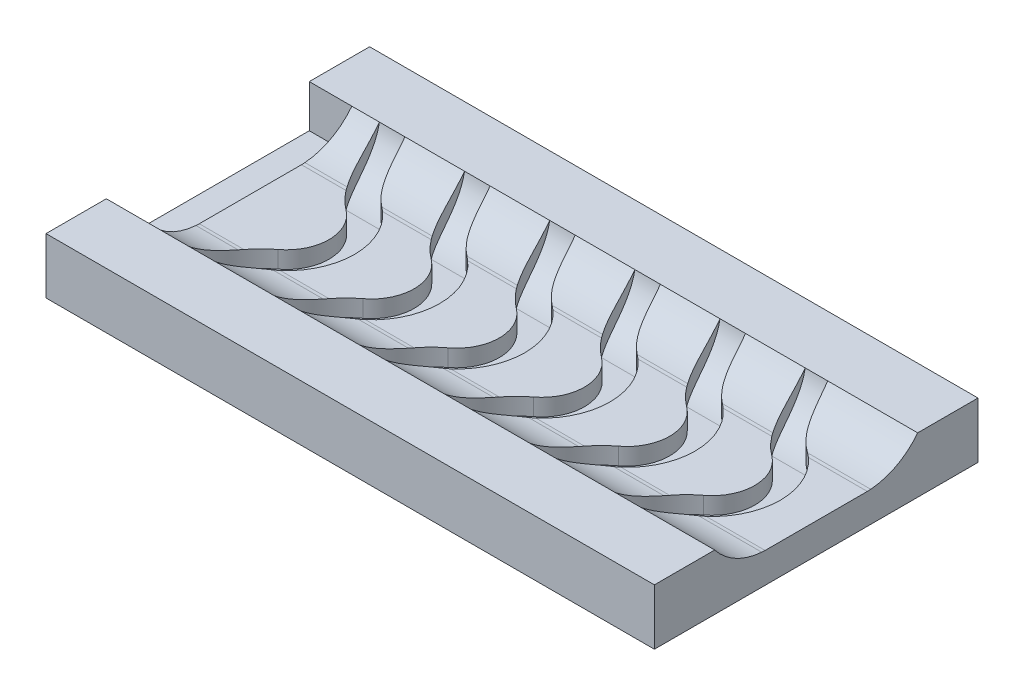
SolidWorks part; units mm, degrees
ref_plane "Front Plane" through (0, 0, 0) normal (0, 0, 1) x (1, 0, 0)
ref_plane "Top Plane" through (0, 0, 0) normal (0, 1, 0) x (1, 0, 0)
ref_plane "Right Plane" through (0, 0, 0) normal (1, 0, 0) x (0, 0, -1)
sketch "Sketch1" plane through (0, 0, 0) normal (0, 1, 0) x (1, 0, 0)
  line L0 (-64.0369, -7.1498) -> (-64.0369, -31.1498)
  line L1 (-64.0369, -31.1498) -> (-8.0369, -31.1498)
  line L2 (-8.0369, -31.1498) -> (-8.0369, -7.1498)
  line L3 (-8.0369, -7.1498) -> (-64.0369, -7.1498)
  line L4 (-8.0369, -31.1498) -> (-8.0369, -38.1498)
  line L5 (-8.0369, -38.1498) -> (-71.0369, -38.1498)
  line L6 (-71.0369, -38.1498) -> (-71.0369, -0.1498)
  line L7 (-71.0369, -0.1498) -> (-1.0369, -0.1498)
  line L8 (-1.0369, -0.1498) -> (-1.0369, -38.1498)
  line L9 (-1.0369, -38.1498) -> (-8.0369, -38.1498)
extrude "Boss-Extrude1" add sketch "Sketch1" along normal blind 10 contours L9 L8 L7 L6 L5 L1 L0 L3 L2 region at (-39.5369, 0, 37.3533)
sketch "Sketch2" plane through (0, 0, 0) normal (0, -1, 0) x (1, 0, 0)
  line L4 (-71.0369, 38.1498) -> (-71.0369, 0.1498)
  line L5 (-71.0369, 0.1498) -> (-1.0369, 0.1498)
  line L6 (-1.0369, 0.1498) -> (-1.0369, 38.1498)
  line L7 (-1.0369, 38.1498) -> (-71.0369, 38.1498)
  line L8 (-71.0369, 38.1498) -> (-71.0369, 0.1498)
  line L9 (-71.0369, 0.1498) -> (-1.0369, 0.1498)
  line L10 (-1.0369, 0.1498) -> (-1.0369, 38.1498)
  line L11 (-1.0369, 38.1498) -> (-71.0369, 38.1498)
  dimension "D1" = 0
extrude "Boss-Extrude2" add sketch "Sketch2" against normal blind 7
sketch "Sketch3" plane through (0, 7, 0) normal (0, 1, 0) x (1, 0, 0)
  line L0 (-64.0369, -19.1498) -> (-8.0369, -19.1498)
  line L1 (-64.0369, -7.1498) -> (-64.0369, -31.1498) construction
  line L2 (-8.0369, -7.1498) -> (-8.0369, -31.1498) construction
  line L3 (-64.0369, -19.1498) -> (-64.0369, -31.1498)
  line L4 (-64.0369, -19.1498) -> (-64.0369, -7.1498)
  line L8 (-50.2791, -19.1498) -> (-51.4339, -19.1498)
  circle A14 centre (-18.2485, -19.1498) radius 5
  circle A15 centre (-18.2485, -19.1498) radius 8
  circle A16 centre (-18.2485, -19.1498) radius 15
  circle A17 centre (-9.2485, -7.1498) radius 10
  circle A18 centre (-9.6097, -6.8872) radius 7
  circle A19 centre (-9.2485, -31.1498) radius 7
  circle A20 centre (-9.2485, -31.1498) radius 10
  line M7 (-8.0369, -7.1498) -> (-64.0369, -7.1498)
  line M9 (-64.0369, -31.1498) -> (-8.0369, -31.1498)
extrude "Cut-Extrude8" cut sketch "Sketch3" against normal blind 2 contours A20 A15 L0 A14 | A17 A14 L0 A15 | A15 A17 | A18 A17 A15 M7 | A15 A20 | A15 A20 A19 M9 region at (-17.2418, 7, 28.9232) region at (-17.3783, 7, 9.3878) region at (-14.3694, 7, 24.3219) region at (-14.3694, 7, 13.9776) region at (-12.1287, 7, 20.5083) region at (-12.1287, 7, 17.7912)
sketch "Sketch4" plane through (0, 7, 0) normal (0, 1, 0) x (1, 0, 0)
  line L0 (-13.2485, -19.1498) -> (-28.2485, -19.1498)
  line L1 (-16.6047, -7.1498) -> (-8.0369, -7.1498) construction
  line L2 (-64.0369, -31.1498) -> (-8.0369, -31.1498) construction
  arc A0 (-15.2485, -23.1498) -> (-15.2485, -15.1498) centre (-18.2485, -19.1498) ccw construction
  circle A1 centre (-28.2485, -19.1498) radius 5
  circle A2 centre (-28.2485, -19.1498) radius 8
  circle A3 centre (-28.2485, -19.1498) radius 15
  circle A4 centre (-19.2485, -7.1498) radius 10
  circle A5 centre (-19.2485, -7.1498) radius 7
  circle A6 centre (-19.2485, -31.1498) radius 10
  circle A7 centre (-19.2485, -31.1498) radius 7
  line M5 (-19.2485, -7.1498) -> (-64.0369, -7.1498)
  line M7 (-64.0369, -31.1498) -> (-19.2485, -31.1498)
extrude "Cut-Extrude10" cut sketch "Sketch4" against normal blind 2 contours A5 A4 A2 M5 | A2 A4 | A4 A1 L0 A2 | A6 A2 L0 A1 | A2 A6 | A7 A2 A6 M7 region at (-22.1287, 7, 20.5083) region at (-22.1287, 7, 17.7912) region at (-24.3694, 7, 13.9776) region at (-24.3694, 7, 24.3219) region at (-27.2418, 7, 9.3764) region at (-27.2418, 7, 28.9232)
sketch "Sketch5" plane through (0, 7, 0) normal (0, 1, 0) x (1, 0, 0)
  line L0 (-23.2485, -19.1498) -> (-38.2485, -19.1498)
  arc A0 (-25.2485, -23.1498) -> (-25.2485, -15.1498) centre (-28.2485, -19.1498) ccw construction
  circle A1 centre (-38.2485, -19.1498) radius 5
  circle A2 centre (-38.2485, -19.1498) radius 8
  circle A3 centre (-38.2485, -19.1498) radius 15
  circle A4 centre (-29.2485, -31.1498) radius 10
  circle A5 centre (-29.2485, -31.1498) radius 7
  circle A6 centre (-29.2485, -7.1498) radius 10
  circle A7 centre (-29.2485, -7.1498) radius 7
  line M4 (-64.0369, -31.1498) -> (-29.2485, -31.1498)
  line M8 (-29.2485, -7.1498) -> (-64.0369, -7.1498)
extrude "Cut-Extrude11" cut sketch "Sketch5" against normal blind 2 contours A7 A6 A2 M8 | A2 A6 | A6 A1 L0 A2 | A4 A2 L0 A1 | A2 A4 | A5 A2 A4 M4 region at (-32.1287, 7, 20.5083) region at (-32.1287, 7, 17.7912) region at (-34.3694, 7, 13.9776) region at (-34.3694, 7, 24.3219) region at (-37.2418, 7, 9.3764) region at (-37.2418, 7, 28.9232)
sketch "Sketch6" plane through (0, 7, 0) normal (0, 1, 0) x (1, 0, 0)
  line L0 (-33.2485, -19.1498) -> (-48.2485, -19.1498)
  arc A0 (-35.2485, -23.1498) -> (-35.2485, -15.1498) centre (-38.2485, -19.1498) ccw construction
  circle A1 centre (-48.2485, -19.1498) radius 5
  circle A2 centre (-48.2485, -19.1498) radius 8
  circle A3 centre (-48.2485, -19.1498) radius 15
  circle A4 centre (-39.2485, -31.1498) radius 10
  circle A5 centre (-39.2485, -31.1498) radius 7
  circle A6 centre (-39.2485, -7.1498) radius 10
  arc A7 (-39.2485, -7.1498) -> (-35.2485, -15.1498) centre (-29.2485, -7.1498) ccw construction
  circle A8 centre (-39.2485, -7.1498) radius 7
  line M1 (-64.0369, -31.1498) -> (-39.2485, -31.1498)
  line M5 (-39.2485, -7.1498) -> (-64.0369, -7.1498)
extrude "Cut-Extrude12" cut sketch "Sketch6" against normal blind 2 contours A8 A6 A2 M5 | A2 A6 | A6 A1 L0 A2 | A4 A2 L0 A1 | A2 A4 | A5 A2 A4 M1 region at (-42.1287, 7, 20.5083) region at (-42.1287, 7, 17.7912) region at (-44.3694, 7, 13.9776) region at (-44.3694, 7, 24.3219) region at (-47.2418, 7, 9.3764) region at (-47.2418, 7, 28.9232)
sketch "Sketch7" plane through (0, 7, 0) normal (0, 1, 0) x (1, 0, 0)
  line L0 (-43.2485, -19.1498) -> (-58.2485, -19.1498)
  arc A0 (-45.2485, -23.1498) -> (-45.2485, -15.1498) centre (-48.2485, -19.1498) ccw construction
  circle A1 centre (-58.2485, -19.1498) radius 5
  circle A2 centre (-58.2485, -19.1498) radius 8
  circle A3 centre (-58.2485, -19.1498) radius 15
  circle A4 centre (-49.2485, -31.1498) radius 10
  circle A5 centre (-49.2485, -31.1498) radius 7
  circle A6 centre (-49.2485, -7.1498) radius 10
  circle A7 centre (-49.2485, -7.1498) radius 7
  line M1 (-64.0369, -31.1498) -> (-49.2485, -31.1498)
  line M5 (-49.2485, -7.1498) -> (-64.0369, -7.1498)
extrude "Cut-Extrude13" cut sketch "Sketch7" against normal blind 2 contours A7 A6 A2 M5 | A2 A6 | A6 A1 L0 A2 | A4 A2 L0 A1 | A2 A4 | A5 A2 A4 M1 region at (-52.1287, 7, 20.5083) region at (-52.1287, 7, 17.7912) region at (-54.3694, 7, 13.9776) region at (-54.3694, 7, 24.3219) region at (-57.2418, 7, 9.3764) region at (-57.2418, 7, 28.9232)
sketch "Sketch8" plane through (0, 7, 0) normal (0, 1, 0) x (1, 0, 0)
  line L0 (-53.2485, -19.1498) -> (-68.2485, -19.1498)
  arc A0 (-55.2485, -23.1498) -> (-55.2485, -15.1498) centre (-58.2485, -19.1498) ccw construction
  circle A1 centre (-68.2485, -19.1498) radius 5
  circle A2 centre (-68.2485, -19.1498) radius 8
  line M6 (-64.0369, -7.1498) -> (-64.0369, -31.1498)
extrude "Cut-Extrude14" cut sketch "Sketch8" against normal blind 2 contours L0 A2 A1 M6 | A2 L0 A1 M6 region at (-62.3799, 7, 21.9464) region at (-62.3799, 7, 16.3531)
sketch "Sketch9" plane through (0, 10, 0) normal (0, 1, 0) x (1, 0, 0)
  line L0 (-8.0369, -7.1498) -> (-5.1643, -7.1498)
  line L1 (-5.1643, -7.1498) -> (-5.1643, -31.1498)
  line L2 (-5.1643, -31.1498) -> (-8.0369, -31.1498)
  line L3 (-8.0369, -31.1498) -> (-8.0369, -7.1498)
extrude "Cut-Extrude15" cut sketch "Sketch9" against normal blind 5
sketch "Sketch10" plane through (-5.1643, 0, 0) normal (-1, 0, 0) x (0, 0, 1)
  line L4 (31.1498, 10) -> (7.1498, 10)
  line L5 (7.1498, 10) -> (7.1498, 5)
  line L6 (7.1498, 5) -> (31.1498, 5)
  line L7 (31.1498, 5) -> (31.1498, 10)
  line L8 (31.1498, 10) -> (7.1498, 10)
  line L9 (7.1498, 10) -> (7.1498, 5)
  line L10 (7.1498, 5) -> (31.1498, 5)
  line L11 (31.1498, 5) -> (31.1498, 10)
  dimension "D1" = 0
extrude "Cut-Extrude16" cut sketch "Sketch10" against normal blind 18
sketch "Sketch12" plane through (0, 7, 0) normal (0, 1, 0) x (1, 0, 0)
  line L0 (-16.2485, -31.1498) -> (-8.0369, -31.1498) construction
  line L1 (-8.0369, -31.1498) -> (-8.0369, -7.1498) construction
  line L2 (-8.0369, -7.1498) -> (-16.6047, -7.1498) construction
  line L3 (-26.2485, -31.1498) -> (-19.2485, -31.1498) construction
  line L4 (-19.2485, -7.1498) -> (-26.2485, -7.1498) construction
  line L5 (-36.2485, -31.1498) -> (-29.2485, -31.1498) construction
  line L6 (-29.2485, -7.1498) -> (-36.2485, -7.1498) construction
  line L7 (-46.2485, -31.1498) -> (-39.2485, -31.1498) construction
  line L8 (-39.2485, -7.1498) -> (-46.2485, -7.1498) construction
  line L9 (-56.2485, -31.1498) -> (-49.2485, -31.1498) construction
  line L10 (-49.2485, -7.1498) -> (-56.2485, -7.1498) construction
  line L11 (-64.0369, -7.1498) -> (-64.0369, -12.3481) construction
  line L12 (-64.0369, -25.9514) -> (-64.0369, -31.1498) construction
  line L13 (-64.0369, -31.1498) -> (-59.2485, -31.1498) construction
  line L14 (-59.2485, -7.1498) -> (-64.0369, -7.1498) construction
  line L15 (-64.0369, -16.4548) -> (-64.0369, -21.8447) construction
  line L16 (-16.2485, -31.1498) -> (-8.0369, -31.1498)
  line L17 (-8.0369, -31.1498) -> (-8.0369, -7.1498)
  line L18 (-8.0369, -7.1498) -> (-16.6047, -7.1498)
  line L19 (-26.2485, -31.1498) -> (-19.2485, -31.1498)
  line L20 (-19.2485, -7.1498) -> (-26.2485, -7.1498)
  line L21 (-36.2485, -31.1498) -> (-29.2485, -31.1498)
  line L22 (-29.2485, -7.1498) -> (-36.2485, -7.1498)
  line L23 (-46.2485, -31.1498) -> (-39.2485, -31.1498)
  line L24 (-39.2485, -7.1498) -> (-46.2485, -7.1498)
  line L25 (-56.2485, -31.1498) -> (-49.2485, -31.1498)
  line L26 (-49.2485, -7.1498) -> (-56.2485, -7.1498)
  line L27 (-64.0369, -7.1498) -> (-64.0369, -12.3481)
  line L28 (-64.0369, -25.9514) -> (-64.0369, -31.1498)
  line L29 (-64.0369, -31.1498) -> (-59.2485, -31.1498)
  line L30 (-59.2485, -7.1498) -> (-64.0369, -7.1498)
  line L31 (-64.0369, -16.4548) -> (-64.0369, -21.8447)
  arc A0 (-13.4485, -25.5498) -> (-13.6411, -12.6097) centre (-18.2485, -19.1498) ccw construction
  arc A1 (-13.4485, -25.5498) -> (-16.2485, -31.1498) centre (-9.2485, -31.1498) ccw construction
  arc A2 (-16.6047, -7.1498) -> (-13.6411, -12.6097) centre (-9.6097, -6.8872) ccw construction
  arc A3 (-26.2485, -7.1498) -> (-23.4485, -12.7498) centre (-19.2485, -7.1498) ccw construction
  arc A4 (-23.4485, -25.5498) -> (-23.4485, -12.7498) centre (-28.2485, -19.1498) ccw construction
  arc A5 (-23.4485, -25.5498) -> (-26.2485, -31.1498) centre (-19.2485, -31.1498) ccw construction
  arc A6 (-15.2485, -23.1498) -> (-19.2485, -31.1498) centre (-9.2485, -31.1498) ccw construction
  arc A7 (-15.2485, -23.1498) -> (-15.2485, -15.1498) centre (-18.2485, -19.1498) ccw construction
  arc A8 (-19.2485, -7.1498) -> (-15.2485, -15.1498) centre (-9.2485, -7.1498) ccw construction
  arc A9 (-36.2485, -7.1498) -> (-33.4485, -12.7498) centre (-29.2485, -7.1498) ccw construction
  arc A10 (-33.4485, -25.5498) -> (-33.4485, -12.7498) centre (-38.2485, -19.1498) ccw construction
  arc A11 (-33.4485, -25.5498) -> (-36.2485, -31.1498) centre (-29.2485, -31.1498) ccw construction
  arc A12 (-25.2485, -23.1498) -> (-29.2485, -31.1498) centre (-19.2485, -31.1498) ccw construction
  arc A13 (-25.2485, -23.1498) -> (-25.2485, -15.1498) centre (-28.2485, -19.1498) ccw construction
  arc A14 (-29.2485, -7.1498) -> (-25.2485, -15.1498) centre (-19.2485, -7.1498) ccw construction
  arc A15 (-46.2485, -7.1498) -> (-43.4485, -12.7498) centre (-39.2485, -7.1498) ccw construction
  arc A16 (-43.4485, -25.5498) -> (-43.4485, -12.7498) centre (-48.2485, -19.1498) ccw construction
  arc A17 (-43.4485, -25.5498) -> (-46.2485, -31.1498) centre (-39.2485, -31.1498) ccw construction
  arc A18 (-35.2485, -23.1498) -> (-39.2485, -31.1498) centre (-29.2485, -31.1498) ccw construction
  arc A19 (-35.2485, -23.1498) -> (-35.2485, -15.1498) centre (-38.2485, -19.1498) ccw construction
  arc A20 (-39.2485, -7.1498) -> (-35.2485, -15.1498) centre (-29.2485, -7.1498) ccw construction
  arc A21 (-56.2485, -7.1498) -> (-53.4485, -12.7498) centre (-49.2485, -7.1498) ccw construction
  arc A22 (-53.4485, -25.5498) -> (-53.4485, -12.7498) centre (-58.2485, -19.1498) ccw construction
  arc A23 (-53.4485, -25.5498) -> (-56.2485, -31.1498) centre (-49.2485, -31.1498) ccw construction
  arc A24 (-45.2485, -23.1498) -> (-49.2485, -31.1498) centre (-39.2485, -31.1498) ccw construction
  arc A25 (-45.2485, -23.1498) -> (-45.2485, -15.1498) centre (-48.2485, -19.1498) ccw construction
  arc A26 (-49.2485, -7.1498) -> (-45.2485, -15.1498) centre (-39.2485, -7.1498) ccw construction
  arc A27 (-64.0369, -25.9514) -> (-64.0369, -12.3481) centre (-68.2485, -19.1498) ccw construction
  arc A28 (-55.2485, -23.1498) -> (-59.2485, -31.1498) centre (-49.2485, -31.1498) ccw construction
  arc A29 (-55.2485, -23.1498) -> (-55.2485, -15.1498) centre (-58.2485, -19.1498) ccw construction
  arc A30 (-59.2485, -7.1498) -> (-55.2485, -15.1498) centre (-49.2485, -7.1498) ccw construction
  arc A31 (-64.0369, -21.8447) -> (-64.0369, -16.4548) centre (-68.2485, -19.1498) ccw construction
  arc A32 (-13.4485, -25.5498) -> (-13.6411, -12.6097) centre (-18.2485, -19.1498) ccw
  arc A33 (-13.4485, -25.5498) -> (-16.2485, -31.1498) centre (-9.2485, -31.1498) ccw
  arc A34 (-16.6047, -7.1498) -> (-13.6411, -12.6097) centre (-9.6097, -6.8872) ccw
  arc A35 (-26.2485, -7.1498) -> (-23.4485, -12.7498) centre (-19.2485, -7.1498) ccw
  arc A36 (-23.4485, -25.5498) -> (-23.4485, -12.7498) centre (-28.2485, -19.1498) ccw
  arc A37 (-23.4485, -25.5498) -> (-26.2485, -31.1498) centre (-19.2485, -31.1498) ccw
  arc A38 (-15.2485, -23.1498) -> (-19.2485, -31.1498) centre (-9.2485, -31.1498) ccw
  arc A39 (-15.2485, -23.1498) -> (-15.2485, -15.1498) centre (-18.2485, -19.1498) ccw
  arc A40 (-19.2485, -7.1498) -> (-15.2485, -15.1498) centre (-9.2485, -7.1498) ccw
  arc A41 (-36.2485, -7.1498) -> (-33.4485, -12.7498) centre (-29.2485, -7.1498) ccw
  arc A42 (-33.4485, -25.5498) -> (-33.4485, -12.7498) centre (-38.2485, -19.1498) ccw
  arc A43 (-33.4485, -25.5498) -> (-36.2485, -31.1498) centre (-29.2485, -31.1498) ccw
  arc A44 (-25.2485, -23.1498) -> (-29.2485, -31.1498) centre (-19.2485, -31.1498) ccw
  arc A45 (-25.2485, -23.1498) -> (-25.2485, -15.1498) centre (-28.2485, -19.1498) ccw
  arc A46 (-29.2485, -7.1498) -> (-25.2485, -15.1498) centre (-19.2485, -7.1498) ccw
  arc A47 (-46.2485, -7.1498) -> (-43.4485, -12.7498) centre (-39.2485, -7.1498) ccw
  arc A48 (-43.4485, -25.5498) -> (-43.4485, -12.7498) centre (-48.2485, -19.1498) ccw
  arc A49 (-43.4485, -25.5498) -> (-46.2485, -31.1498) centre (-39.2485, -31.1498) ccw
  arc A50 (-35.2485, -23.1498) -> (-39.2485, -31.1498) centre (-29.2485, -31.1498) ccw
  arc A51 (-35.2485, -23.1498) -> (-35.2485, -15.1498) centre (-38.2485, -19.1498) ccw
  arc A52 (-39.2485, -7.1498) -> (-35.2485, -15.1498) centre (-29.2485, -7.1498) ccw
  arc A53 (-56.2485, -7.1498) -> (-53.4485, -12.7498) centre (-49.2485, -7.1498) ccw
  arc A54 (-53.4485, -25.5498) -> (-53.4485, -12.7498) centre (-58.2485, -19.1498) ccw
  arc A55 (-53.4485, -25.5498) -> (-56.2485, -31.1498) centre (-49.2485, -31.1498) ccw
  arc A56 (-45.2485, -23.1498) -> (-49.2485, -31.1498) centre (-39.2485, -31.1498) ccw
  arc A57 (-45.2485, -23.1498) -> (-45.2485, -15.1498) centre (-48.2485, -19.1498) ccw
  arc A58 (-49.2485, -7.1498) -> (-45.2485, -15.1498) centre (-39.2485, -7.1498) ccw
  arc A59 (-64.0369, -25.9514) -> (-64.0369, -12.3481) centre (-68.2485, -19.1498) ccw
  arc A60 (-55.2485, -23.1498) -> (-59.2485, -31.1498) centre (-49.2485, -31.1498) ccw
  arc A61 (-55.2485, -23.1498) -> (-55.2485, -15.1498) centre (-58.2485, -19.1498) ccw
  arc A62 (-59.2485, -7.1498) -> (-55.2485, -15.1498) centre (-49.2485, -7.1498) ccw
  arc A63 (-64.0369, -21.8447) -> (-64.0369, -16.4548) centre (-68.2485, -19.1498) ccw
extrude "Boss-Extrude3" add sketch "Sketch12" along normal blind 3
sketch "Sketch13" plane through (-1.0369, 0, 0) normal (1, 0, 0) x (0, 0, -1)
  line L0 (-31.1498, 5) -> (-31.1498, 11)
  line L1 (-31.1498, 11) -> (-25.1498, 11)
  line L2 (-7.1498, 5) -> (-7.1498, 11)
  line L3 (-7.1498, 11) -> (-13.1498, 11)
  circle A0 centre (-25.1498, 11) radius 6
  circle A1 centre (-13.1498, 11) radius 6
  line M1 (-31.1498, 5) -> (-31.1498, 10)
  line M7 (-7.1498, 10) -> (-7.1498, 5)
  line M8 (-7.1498, 5) -> (-31.1498, 5)
extrude "Boss-Extrude4" add sketch "Sketch13" against normal blind 149 contours A0 L0 M1 M8 | A1 L2 M8 M7 region at (-1.0369, 6.3402, 29.8095) region at (-1.0369, 6.3402, 8.49)
sketch "Sketch14" plane through (-1.0369, 0, 0) normal (1, 0, 0) x (0, 0, -1)
  line L0 (-25.1498, 7) -> (-13.1498, 7)
  line L1 (-13.1498, 7) -> (-13.1498, 15)
  line L2 (-13.1498, 15) -> (-25.1498, 15)
  circle A0 centre (-25.1498, 11) radius 4
  circle A1 centre (-13.1498, 11) radius 4
extrude "Cut-Extrude17" cut sketch "Sketch14" against normal up to surface (63 mm away) contours A0 | L1 A1 | L1 A1 | A1 L2 A0 L0 region at (-1.0369, 11, 19.1498) region at (-1.0369, 11, 25.1498) region at (-1.0369, 11, 14.8474) region at (-1.0369, 11, 11.4521) up to face at (-64.0369, 7.0081, 24.1486)
sketch "Sketch15" plane through (-1.0369, 0, 0) normal (1, 0, 0) x (0, 0, -1)
  line L0 (-38.1498, 10) -> (-0.1498, 10)
  line L1 (-0.1498, 10) -> (-0.1498, 15.8218)
  line L2 (-0.1498, 15.8218) -> (-38.1498, 15.8218)
  line L3 (-38.1498, 15.8218) -> (-38.1498, 10)
extrude "Cut-Extrude18" cut sketch "Sketch15" against normal blind 103
sketch "Sketch16" plane through (-1.0369, 0, 0) normal (1, 0, 0) x (0, 0, -1)
  line L1 (-38.1498, 0) -> (-0.1498, 0)
  line L2 (-38.1498, 0) -> (-38.1498, 10)
  line L3 (-38.1498, 10) -> (-0.1498, 10)
  line L4 (-0.1498, 0) -> (-0.1498, 10)
extrude "Boss-Extrude5" add sketch "Sketch16" against normal up to surface (7 mm away) up to face at (-8.0369, 7.5638, 19.1498)
sketch "Sketch17" plane through (-64.0369, 0, 0) normal (1, 0, 0) x (0, 0, -1)
  line L0 (-21.8447, 5) -> (-16.4548, 5)
  line L8 (-12.3481, 5.0538) -> (-12.3481, 7.0812)
  line L9 (-9.2768, 10) -> (-29.0227, 10)
  line L10 (-25.9514, 7.0812) -> (-25.9514, 5.0538)
  line L11 (-25.1498, 5) -> (-21.8447, 5)
  line L12 (-21.8447, 5) -> (-21.8447, 7)
  line L13 (-21.8447, 7) -> (-16.4548, 7)
  line L14 (-16.4548, 7) -> (-16.4548, 5)
  line L15 (-16.4548, 5) -> (-13.1498, 5)
  line L16 (-12.3481, 5.0538) -> (-12.3481, 7.0812)
  line L17 (-9.2768, 10) -> (-29.0227, 10)
  line L18 (-25.9514, 7.0812) -> (-25.9514, 5.0538)
  line L19 (-25.1498, 5) -> (-21.8447, 5)
  line L20 (-21.8447, 5) -> (-21.8447, 7)
  line L21 (-21.8447, 7) -> (-16.4548, 7)
  line L22 (-16.4548, 7) -> (-16.4548, 5)
  line L23 (-16.4548, 5) -> (-13.1498, 5)
  arc A4 (-12.3481, 7.0812) -> (-9.2768, 10) centre (-13.1498, 11) ccw
  arc A5 (-29.0227, 10) -> (-25.9514, 7.0812) centre (-25.1498, 11) ccw
  arc A6 (-25.9514, 5.0538) -> (-25.1498, 5) centre (-25.1498, 11) ccw
  arc A7 (-13.1498, 5) -> (-12.3481, 5.0538) centre (-13.1498, 11) ccw
  arc A8 (-12.3481, 7.0812) -> (-9.2768, 10) centre (-13.1498, 11) ccw
  arc A9 (-29.0227, 10) -> (-25.9514, 7.0812) centre (-25.1498, 11) ccw
  arc A10 (-25.9514, 5.0538) -> (-25.1498, 5) centre (-25.1498, 11) ccw
  arc A11 (-13.1498, 5) -> (-12.3481, 5.0538) centre (-13.1498, 11) ccw
  line M13 (-12.3481, 5.0538) -> (-12.3481, 7.0812)
  arc M14 (-12.3481, 7.0812) -> (-9.2768, 10) centre (-13.1498, 11) ccw
  line M15 (-9.2768, 10) -> (-29.0227, 10)
  arc M16 (-29.0227, 10) -> (-25.9514, 7.0812) centre (-25.1498, 11) ccw
  line M17 (-25.9514, 7.0812) -> (-25.9514, 5.0538)
  arc M18 (-25.9514, 5.0538) -> (-25.1498, 5) centre (-25.1498, 11) ccw
  line M19 (-25.1498, 5) -> (-21.8447, 5)
  line M20 (-21.8447, 5) -> (-21.8447, 7)
  line M21 (-21.8447, 7) -> (-16.4548, 7)
  line M22 (-16.4548, 7) -> (-16.4548, 5)
  line M23 (-16.4548, 5) -> (-13.1498, 5)
  arc M24 (-13.1498, 5) -> (-12.3481, 5.0538) centre (-13.1498, 11) ccw
  dimension "D1" = 0
extrude "Cut-Extrude19" cut sketch "Sketch17" against normal blind 12 contours M24 M13 M14 M15 M16 M17 M18 M19 M20 M21 M22 M23 | L0 M20 M22 M21 region at (-64.0369, 6, 19.1498) region at (-64.0369, 7.9729, 19.1498)
sketch "Sketch18" plane through (0, 7, 0) normal (0, 1, 0) x (1, 0, 0)
  line L1 (-64.0369, -16.4548) -> (-64.0369, -21.8447)
  line L2 (-64.0369, -16.4548) -> (-64.0369, -21.8447)
  arc A1 (-64.0369, -21.8447) -> (-64.0369, -16.4548) centre (-68.2485, -19.1498) ccw
  arc A2 (-64.0369, -21.8447) -> (-64.0369, -16.4548) centre (-68.2485, -19.1498) ccw
  dimension "D1" = 0
extrude "Cut-Extrude20" cut sketch "Sketch18" against normal up to surface (2 mm away) up to face at (-14.3903, 5, 19.1498)
sketch "Sketch19" plane through (-71.0369, 0, 0) normal (-1, 0, 0) x (0, 0, 1)
  line L8 (13.1498, 5) -> (7.1498, 5)
  line L9 (25.1498, 5) -> (13.1498, 5)
  line L10 (13.1498, 5) -> (7.1498, 5)
  line L11 (7.1498, 5) -> (7.1498, 10)
  line L12 (0.1498, 10) -> (0.1498, 0)
  line L13 (0.1498, 0) -> (38.1498, 0)
  line L14 (38.1498, 0) -> (38.1498, 10)
  line L15 (38.1498, 10) -> (31.1498, 10)
  line L17 (25.1498, 5) -> (13.1498, 5)
  line L20 (0.1498, 10) -> (0.1498, 0)
  line L21 (0.1498, 0) -> (38.1498, 0)
  line L22 (38.1498, 0) -> (38.1498, 10)
  line L23 (38.1498, 10) -> (31.1498, 10)
  line L26 (7.1498, 5) -> (7.1498, 10)
  line L27 (7.1498, 10) -> (0.1498, 10)
  line L28 (7.1498, 10) -> (0.1498, 10)
  line L29 (31.1498, 10) -> (31.1498, 5)
  line L30 (31.1498, 10) -> (31.1498, 5)
  line L31 (31.1498, 5) -> (25.1498, 5)
  line L32 (31.1498, 5) -> (25.1498, 5)
  circle A0 centre (13.1498, 11) radius 6
  circle A1 centre (25.1498, 11) radius 6
  line M16 (25.1498, 5) -> (13.1498, 5)
  line M21 (0.1498, 10) -> (0.1498, 0)
  line M22 (0.1498, 0) -> (38.1498, 0)
  line M23 (38.1498, 0) -> (38.1498, 10)
  line M24 (38.1498, 10) -> (31.1498, 10)
  dimension "D1" = 0
extrude "Boss-Extrude6" add sketch "Sketch19" along normal blind 15 contours A1 A0 M16 M21 M22 M23 M24 region at (-71.0369, 3.8462, 19.1498)
sketch "Sketch23" plane through (0, 10, 0) normal (0, 1, 0) x (1, 0, 0)
  line L0 (-53.2485, -19.1498) -> (-68.2485, -19.1498)
  line L1 (-46.248, -7.2337) -> (-91.0802, -7.2337)
  line L2 (-56.248, -31.0658) -> (-91.0802, -31.0658)
  arc A0 (-55.2485, -23.1498) -> (-55.2485, -15.1498) centre (-58.2485, -19.1498) ccw construction
  circle A1 centre (-68.2485, -19.1498) radius 5
  circle A2 centre (-68.2485, -19.1498) radius 8
  circle A3 centre (-68.2485, -19.1498) radius 15
  circle A4 centre (-59.2482, -7.2337) radius 9.9332
  circle A5 centre (-59.2482, -7.2337) radius 6.9332
  circle A6 centre (-59.2482, -31.0658) radius 9.9332
  circle A7 centre (-59.2482, -31.0658) radius 6.9332
extrude "Cut-Extrude21" cut sketch "Sketch23" against normal blind 5 contours A5 L1 A4 A2 | A2 A4 | A4 A1 L0 A2 | A6 A2 L0 A1 | A2 A6 | A7 A2 A6 L2 region at (-62.1275, 10, 20.5007) region at (-62.1275, 10, 17.7988) region at (-64.3512, 10, 13.9899) region at (-64.3512, 10, 24.3096) region at (-67.1841, 10, 9.4203) region at (-67.1841, 10, 28.8792)
sketch "Sketch24" plane through (0, 7, 0) normal (0, 1, 0) x (1, 0, 0)
  line L5 (-62.957, -25.1498) -> (-57.2485, -25.1498)
  line L6 (-57.2485, -13.1498) -> (-62.957, -13.1498)
  line L9 (-62.957, -25.1498) -> (-57.2485, -25.1498)
  line L10 (-57.2485, -13.1498) -> (-62.957, -13.1498)
  line L12 (-65.8735, -29.0227) -> (-59.0197, -29.0227)
  line L13 (-57.2485, -25.1498) -> (-62.957, -25.1498)
  line L15 (-65.8735, -29.0227) -> (-59.0197, -29.0227)
  line L16 (-57.2485, -25.1498) -> (-62.957, -25.1498)
  line L18 (-62.957, -13.1498) -> (-57.2485, -13.1498)
  line L19 (-59.0197, -9.2768) -> (-65.8735, -9.2768)
  line L21 (-62.957, -13.1498) -> (-57.2485, -13.1498)
  line L22 (-59.0197, -9.2768) -> (-65.8735, -9.2768)
  arc A1 (-57.2485, -25.1498) -> (-59.0197, -29.0227) centre (-49.2485, -31.1498) ccw
  arc A2 (-57.2485, -25.1498) -> (-59.0197, -29.0227) centre (-49.2485, -31.1498) ccw
  arc A3 (-59.0197, -9.2768) -> (-57.2485, -13.1498) centre (-49.2485, -7.1498) ccw
  arc A4 (-55.2485, -23.1498) -> (-57.2485, -25.1498) centre (-49.2485, -31.1498) ccw
  arc A5 (-55.2485, -23.1498) -> (-55.2485, -15.1498) centre (-58.2485, -19.1498) ccw
  arc A6 (-57.2485, -13.1498) -> (-55.2485, -15.1498) centre (-49.2485, -7.1498) ccw
  arc A7 (-62.957, -25.1498) -> (-62.957, -13.1498) centre (-68.2485, -19.1498) ccw
  arc A8 (-55.2485, -23.1498) -> (-57.2485, -25.1498) centre (-49.2485, -31.1498) ccw
  arc A9 (-55.2485, -23.1498) -> (-55.2485, -15.1498) centre (-58.2485, -19.1498) ccw
  arc A10 (-57.2485, -13.1498) -> (-55.2485, -15.1498) centre (-49.2485, -7.1498) ccw
  arc A11 (-62.957, -25.1498) -> (-62.957, -13.1498) centre (-68.2485, -19.1498) ccw
  arc A12 (-59.0197, -9.2768) -> (-57.2485, -13.1498) centre (-49.2485, -7.1498) ccw
  arc A15 (-63.4268, -25.5334) -> (-65.8735, -29.0227) centre (-59.2482, -31.0658) ccw
  arc A16 (-63.4268, -25.5334) -> (-65.8735, -29.0227) centre (-59.2482, -31.0658) ccw
  arc A17 (-63.4268, -25.5334) -> (-62.957, -25.1498) centre (-68.2485, -19.1498) ccw
  arc A18 (-63.4268, -25.5334) -> (-62.957, -25.1498) centre (-68.2485, -19.1498) ccw
  arc A19 (-65.8735, -9.2768) -> (-63.4268, -12.7661) centre (-59.2482, -7.2337) ccw
  arc A20 (-65.8735, -9.2768) -> (-63.4268, -12.7661) centre (-59.2482, -7.2337) ccw
  arc A21 (-62.957, -13.1498) -> (-63.4268, -12.7661) centre (-68.2485, -19.1498) ccw
  arc A22 (-62.957, -13.1498) -> (-63.4268, -12.7661) centre (-68.2485, -19.1498) ccw
  line M18 (-62.957, -25.1498) -> (-57.2485, -25.1498)
  arc M19 (-57.2485, -25.1498) -> (-55.2485, -23.1498) centre (-49.2485, -31.1498) cw
  arc M20 (-55.2485, -23.1498) -> (-55.2485, -15.1498) centre (-58.2485, -19.1498) ccw
  arc M21 (-55.2485, -15.1498) -> (-57.2485, -13.1498) centre (-49.2485, -7.1498) cw
  line M22 (-57.2485, -13.1498) -> (-62.957, -13.1498)
  arc M24 (-62.957, -13.1498) -> (-62.957, -25.1498) centre (-68.2485, -19.1498) cw
  dimension "D1" = 0
  dimension "D2" = 0
  dimension "D3" = 0
extrude "Boss-Extrude9" add sketch "Sketch24" along normal up to surface (3 mm away) contours M24 M18 M19 M20 M21 M22 | A12 L22 M22 | A2 L15 M18 region at (-57.7948, 7, 19.1498) region at (-61.5621, 7, 27.1419) region at (-61.5621, 7, 11.1577) up to face at (-48.586, 10, 19.1498)
sketch "Sketch25" plane through (0, 10, 0) normal (0, 1, 0) x (1, 0, 0)
  line L0 (-72.4818, -7.2337) -> (-61.5817, -7.2337)
  line L1 (-61.5817, -7.2337) -> (-59.5665, -14.3409)
  line L2 (-59.5665, -14.3409) -> (-58.1763, -19.2443)
  line L3 (-58.1763, -19.2443) -> (-61.5817, -28.3553)
  line L4 (-61.5817, -28.3553) -> (-64.4212, -33.3932)
  line L5 (-64.4212, -33.3932) -> (-72.4818, -33.3932)
  line L6 (-72.4818, -33.3932) -> (-72.4818, -7.2337)
extrude "Boss-Extrude10" add sketch "Sketch25" against normal up to surface (5 mm away) up to face at (-70.3182, 5, 19.1498)
sketch "Sketch26" plane through (0, 10, 0) normal (0, 1, 0) x (1, 0, 0)
  line L0 (-39.2485, -7.1498) -> (-106.0187, -7.1498)
  line L1 (-39.2485, -31.1498) -> (-93.2896, -31.1498)
  line L2 (-56.248, -31.0658) -> (-106.6534, -31.0658)
  line L3 (-56.248, -7.2337) -> (-121.2325, -7.2337)
  line L5 (-53.2485, -19.1498) -> (-68.2485, -19.1498)
  arc A0 (-55.2485, -23.1498) -> (-55.2485, -15.1498) centre (-58.2485, -19.1498) ccw construction
  circle A1 centre (-68.2485, -19.1498) radius 5
  circle A2 centre (-68.2485, -19.1498) radius 8
  circle A3 centre (-68.2485, -19.1498) radius 15
  circle A4 centre (-39.2485, -7.1498) radius 10
  circle A5 centre (-39.2485, -31.1498) radius 10
  circle A6 centre (-59.2485, -7.1498) radius 10
  circle A7 centre (-59.2485, -7.1498) radius 7
  circle A8 centre (-59.2485, -31.1498) radius 10
  circle A9 centre (-59.2485, -31.1498) radius 7
extrude "Cut-Extrude22" cut sketch "Sketch26" against normal blind 5 contours A7 L3 A6 A2 | A2 A6 | A6 A1 L5 A2 | A8 A2 L5 A1 | A2 A8 | A9 A2 A8 L2 region at (-64.3694, 10, 13.9776) region at (-62.1287, 10, 17.7912) region at (-67.2322, 10, 9.4176) region at (-62.1287, 10, 20.5083) region at (-64.3694, 10, 24.3219) region at (-67.2322, 10, 28.8819)
sketch "Sketch27" plane through (-150.0369, 0, 0) normal (-1, 0, 0) x (0, 0, 1)
  line L2 (7.1498, 11) -> (7.1498, 5)
  line L3 (7.1498, 5) -> (13.1498, 5)
  line L4 (7.1498, 11) -> (7.1498, 5)
  line L5 (7.1498, 5) -> (13.1498, 5)
  line L6 (25.1498, 5) -> (31.1498, 5)
  line L7 (31.1498, 5) -> (31.1498, 11)
  line L8 (25.1498, 5) -> (31.1498, 5)
  line L9 (31.1498, 5) -> (31.1498, 11)
  arc A1 (7.1498, 11) -> (13.1498, 5) centre (13.1498, 11) ccw
  arc A2 (7.1498, 11) -> (13.1498, 5) centre (13.1498, 11) ccw
  arc A3 (25.1498, 5) -> (31.1498, 11) centre (25.1498, 11) ccw
  arc A4 (25.1498, 5) -> (31.1498, 11) centre (25.1498, 11) ccw
  dimension "D1" = 0
  dimension "D2" = 0
extrude "Cut-Extrude23" cut sketch "Sketch27" against normal blind 49
sketch "Sketch28" plane through (-101.0369, 0, 0) normal (-1, 0, 0) x (0, 0, 1)
  line L0 (25.1498, 5) -> (31.1498, 5) construction
  line L1 (31.1498, 5) -> (31.1498, 10) construction
  line L2 (31.1498, 10) -> (31.0658, 10) construction
  line L3 (7.1498, 10) -> (7.1498, 5) construction
  line L4 (7.1498, 5) -> (13.1498, 5) construction
  line L5 (7.2337, 10) -> (7.1498, 10) construction
  line L6 (25.1498, 5) -> (31.1498, 5)
  line L7 (31.1498, 5) -> (31.1498, 10)
  line L8 (31.1498, 10) -> (31.0658, 10)
  line L9 (7.1498, 10) -> (7.1498, 5)
  line L10 (7.1498, 5) -> (13.1498, 5)
  line L11 (7.2337, 10) -> (7.1498, 10)
  arc A0 (25.1498, 5) -> (31.0658, 10) centre (25.1498, 11) ccw construction
  arc A1 (7.2337, 10) -> (13.1498, 5) centre (13.1498, 11) ccw construction
  arc A2 (25.1498, 5) -> (31.0658, 10) centre (25.1498, 11) ccw
  arc A3 (7.2337, 10) -> (13.1498, 5) centre (13.1498, 11) ccw
extrude "Boss-Extrude11" add sketch "Sketch28" against normal blind 120
sketch "Sketch29" plane through (-86.0369, 0, 0) normal (-1, 0, 0) x (0, 0, 1)
  line L0 (13.1498, 7) -> (25.1498, 7)
  line L1 (13.1498, 15) -> (25.1498, 15)
  circle A0 centre (13.1498, 11) radius 4
  circle A1 centre (25.1498, 11) radius 4
extrude "Cut-Extrude25" cut sketch "Sketch29" against normal blind 43 contours A0 | A1 | A1 | A0 | A1 A0 L0 | A1 L1 A0 region at (-86.0369, 11, 19.1498) region at (-86.0369, 11, 13.1498) region at (-86.0369, 11, 25.1498)
sketch "Sketch31" plane through (-101.0369, 0, 0) normal (-1, 0, 0) x (0, 0, 1)
  line L3 (7.1498, 10) -> (7.1498, 5)
  line L4 (7.1498, 5) -> (13.1498, 5)
  line L5 (7.2337, 10) -> (7.1498, 10)
  line L6 (7.1498, 10) -> (7.1498, 5)
  line L7 (7.1498, 5) -> (13.1498, 5)
  line L8 (7.2337, 10) -> (7.1498, 10)
  line L9 (25.1498, 5) -> (31.1498, 5)
  line L10 (31.1498, 5) -> (31.1498, 10)
  line L11 (31.1498, 10) -> (31.0658, 10)
  line L12 (25.1498, 5) -> (31.1498, 5)
  line L13 (31.1498, 5) -> (31.1498, 10)
  line L14 (31.1498, 10) -> (31.0658, 10)
  arc A1 (7.2337, 10) -> (13.1498, 5) centre (13.1498, 11) ccw
  arc A2 (7.2337, 10) -> (13.1498, 5) centre (13.1498, 11) ccw
  arc A3 (25.1498, 5) -> (31.0658, 10) centre (25.1498, 11) ccw
  arc A4 (25.1498, 5) -> (31.0658, 10) centre (25.1498, 11) ccw
  dimension "D1" = 0
  dimension "D2" = 0
extrude "Cut-Extrude27" cut sketch "Sketch31" against normal up to surface (15 mm away) up to face at (-86.0369, 6, 19.1498)
sketch "Sketch32" plane through (18.9631, 0, 0) normal (1, 0, 0) x (0, 0, -1)
  line L0 (-7.1498, 10) -> (-7.2337, 10) construction
  line L1 (-13.1498, 5) -> (-7.1498, 5) construction
  line L2 (-7.1498, 5) -> (-7.1498, 10) construction
  line L3 (-31.0658, 10) -> (-31.1498, 10) construction
  line L4 (-31.1498, 10) -> (-31.1498, 5) construction
  line L5 (-31.1498, 5) -> (-25.1498, 5) construction
  line L6 (-7.1498, 10) -> (-7.2337, 10)
  line L7 (-13.1498, 5) -> (-7.1498, 5)
  line L8 (-7.1498, 5) -> (-7.1498, 10)
  line L9 (-31.0658, 10) -> (-31.1498, 10)
  line L10 (-31.1498, 10) -> (-31.1498, 5)
  line L11 (-31.1498, 5) -> (-25.1498, 5)
  arc A0 (-13.1498, 5) -> (-7.2337, 10) centre (-13.1498, 11) ccw construction
  arc A1 (-31.0658, 10) -> (-25.1498, 5) centre (-25.1498, 11) ccw construction
  arc A2 (-13.1498, 5) -> (-7.2337, 10) centre (-13.1498, 11) ccw
  arc A3 (-31.0658, 10) -> (-25.1498, 5) centre (-25.1498, 11) ccw
sketch "Sketch34" plane through (-86.0369, 0, 0) normal (-1, 0, 0) x (0, 0, 1)
  line L6 (38.1498, 10) -> (31.0658, 10)
  line L7 (25.1498, 5) -> (13.1498, 5)
  line L8 (7.2337, 10) -> (0.1498, 10)
  line L9 (0.1498, 10) -> (0.1498, 0)
  line L10 (0.1498, 0) -> (38.1498, 0)
  line L11 (38.1498, 0) -> (38.1498, 10)
  line L12 (38.1498, 10) -> (31.0658, 10)
  line L14 (7.2337, 10) -> (0.1498, 10)
  line L15 (0.1498, 10) -> (0.1498, 0)
  line L16 (0.1498, 0) -> (38.1498, 0)
  line L17 (38.1498, 0) -> (38.1498, 10)
  line L18 (25.1498, 5) -> (13.1498, 5)
  arc A2 (25.1498, 5) -> (31.0658, 10) centre (25.1498, 11) ccw
  arc A6 (25.1498, 5) -> (31.0658, 10) centre (25.1498, 11) ccw
  arc A8 (7.2337, 10) -> (13.1498, 5) centre (13.1498, 11) ccw
  arc A9 (7.2337, 10) -> (13.1498, 5) centre (13.1498, 11) ccw
  dimension "D1" = 0
extrude "Cut-Extrude33" cut sketch "Sketch34" against normal up to surface (13.5551 mm away) up to face at (-72.4818, 7.5638, 19.1498)
extrude "Cut-Extrude34" cut sketch "Sketch32" against normal up to surface (20 mm away) up to face at (-1.0369, 6.4862, 19.1498)
sketch "Sketch43" plane through (-1.0369, 0, 0) normal (1, 0, 0) x (0, 0, -1)
  line L4 (-0.1498, 10) -> (-38.1498, 10)
  line L5 (-38.1498, 10) -> (-38.1498, 0)
  line L6 (-38.1498, 0) -> (-0.1498, 0)
  line L7 (-0.1498, 0) -> (-0.1498, 10)
  line L8 (-0.1498, 10) -> (-38.1498, 10)
  line L9 (-38.1498, 10) -> (-38.1498, 0)
  line L10 (-38.1498, 0) -> (-0.1498, 0)
  line L11 (-0.1498, 0) -> (-0.1498, 10)
  dimension "D1" = 0
extrude "Cut-Extrude35" cut sketch "Sketch43" against normal up to surface (7 mm away) up to face at (-8.0369, 8.1689, 19.1498)
sketch "Sketch44" plane through (-8.0369, 0, 0) normal (1, 0, 0) x (0, 0, -1)
  line L3 (-19.1498, 7) -> (-25.1498, 7)
  line L4 (-13.1498, 7) -> (-25.1498, 7) construction
  line L5 (-25.1498, 7) -> (-19.1498, 7)
  line L6 (-19.1498, 7) -> (-13.1498, 7)
  line L13 (-13.1498, 7) -> (-25.1498, 7)
  line L14 (-29.0227, 10) -> (-38.1498, 10)
  line L15 (-38.1498, 10) -> (-38.1498, 0)
  line L16 (-38.1498, 0) -> (-0.1498, 0)
  line L17 (-0.1498, 0) -> (-0.1498, 10)
  line L18 (-0.1498, 10) -> (-9.2768, 10)
  line L19 (-13.1498, 7) -> (-25.1498, 7)
  line L20 (-29.0227, 10) -> (-38.1498, 10)
  line L21 (-38.1498, 10) -> (-38.1498, 0)
  line L22 (-38.1498, 0) -> (-0.1498, 0)
  line L23 (-0.1498, 0) -> (-0.1498, 10)
  line L24 (-0.1498, 10) -> (-9.2768, 10)
  arc A0 (-31.0658, 10) -> (-25.1498, 7) centre (-24.9643, 14.699) ccw
  arc A1 (-7.2337, 10) -> (-13.1498, 7) centre (-13.3352, 14.699) cw
  arc A4 (-29.0227, 10) -> (-25.1498, 7) centre (-25.1498, 11) ccw
  arc A5 (-13.1498, 7) -> (-9.2768, 10) centre (-13.1498, 11) ccw
  arc A6 (-29.0227, 10) -> (-25.1498, 7) centre (-25.1498, 11) ccw
  arc A7 (-13.1498, 7) -> (-9.2768, 10) centre (-13.1498, 11) ccw
  arc M12 (-25.1498, 7) -> (-29.0227, 10) centre (-25.1498, 11) cw
  line M13 (-29.0227, 10) -> (-38.1498, 10)
  arc M18 (-9.2768, 10) -> (-13.1498, 7) centre (-13.1498, 11) cw
  dimension "D1" = 0
extrude "Cut-Extrude38" cut sketch "Sketch44" against normal blind 67 contours A0 M13 M12 | A1 L24 M18 region at (-8.0369, 8.8806, 29.1215) region at (-8.0369, 8.8806, 9.178)
sketch "Sketch45" plane through (-8.0369, 0, 0) normal (1, 0, 0) x (0, 0, -1)
  line L6 (-31.0658, 10) -> (-38.1498, 10)
  line L7 (-38.1498, 10) -> (-38.1498, 0)
  line L8 (-38.1498, 0) -> (-0.1498, 0)
  line L9 (-0.1498, 0) -> (-0.1498, 10)
  line L10 (-0.1498, 10) -> (-7.2337, 10)
  line L11 (-13.1498, 7) -> (-25.1498, 7)
  line L12 (-31.0658, 10) -> (-38.1498, 10)
  line L13 (-38.1498, 10) -> (-38.1498, 0)
  line L14 (-38.1498, 0) -> (-0.1498, 0)
  line L15 (-0.1498, 0) -> (-0.1498, 10)
  line L16 (-0.1498, 10) -> (-7.2337, 10)
  line L17 (-13.1498, 7) -> (-25.1498, 7)
  arc A4 (-25.5498, 7.0201) -> (-25.1498, 7) centre (-25.1498, 11) ccw
  arc A5 (-31.0658, 10) -> (-25.5498, 7.0201) centre (-24.9643, 14.699) ccw
  arc A6 (-12.7498, 7.0201) -> (-7.2337, 10) centre (-13.3352, 14.699) ccw
  arc A7 (-13.1498, 7) -> (-12.7498, 7.0201) centre (-13.1498, 11) ccw
  arc A8 (-25.5498, 7.0201) -> (-25.1498, 7) centre (-25.1498, 11) ccw
  arc A9 (-31.0658, 10) -> (-25.5498, 7.0201) centre (-24.9643, 14.699) ccw
  arc A10 (-12.7498, 7.0201) -> (-7.2337, 10) centre (-13.3352, 14.699) ccw
  arc A11 (-13.1498, 7) -> (-12.7498, 7.0201) centre (-13.1498, 11) ccw
  dimension "D1" = 0
extrude "Boss-Extrude16" add sketch "Sketch45" along normal blind 2
sketch "Sketch46" plane through (-6.0369, 0, 0) normal (1, 0, 0) x (0, 0, -1)
  line L0 (-38.1498, 3.4493) -> (-0.1498, 3.4493)
  line L6 (-31.0658, 10) -> (-38.1498, 10)
  line L7 (-38.1498, 10) -> (-38.1498, 0)
  line L8 (-38.1498, 0) -> (-0.1498, 0)
  line L9 (-0.1498, 0) -> (-0.1498, 10)
  line L10 (-0.1498, 10) -> (-7.2337, 10)
  line L11 (-13.1498, 7) -> (-25.1498, 7)
  line L12 (-31.0658, 10) -> (-38.1498, 10)
  line L13 (-38.1498, 10) -> (-38.1498, 0)
  line L14 (-38.1498, 0) -> (-0.1498, 0)
  line L15 (-0.1498, 0) -> (-0.1498, 10)
  line L16 (-0.1498, 10) -> (-7.2337, 10)
  line L17 (-13.1498, 7) -> (-25.1498, 7)
  arc A4 (-31.0658, 10) -> (-25.5498, 7.0201) centre (-24.9643, 14.699) ccw
  arc A5 (-12.7498, 7.0201) -> (-7.2337, 10) centre (-13.3352, 14.699) ccw
  arc A6 (-13.1498, 7) -> (-12.7498, 7.0201) centre (-13.1498, 11) ccw
  arc A7 (-25.5498, 7.0201) -> (-25.1498, 7) centre (-25.1498, 11) ccw
  arc A8 (-31.0658, 10) -> (-25.5498, 7.0201) centre (-24.9643, 14.699) ccw
  arc A9 (-12.7498, 7.0201) -> (-7.2337, 10) centre (-13.3352, 14.699) ccw
  arc A10 (-13.1498, 7) -> (-12.7498, 7.0201) centre (-13.1498, 11) ccw
  arc A11 (-25.5498, 7.0201) -> (-25.1498, 7) centre (-25.1498, 11) ccw
  line M13 (-38.1498, 10) -> (-38.1498, 0)
  line M14 (-38.1498, 0) -> (-0.1498, 0)
  line M15 (-0.1498, 0) -> (-0.1498, 10)
  dimension "D1" = 0
extrude "Cut-Extrude39" cut sketch "Sketch46" against normal blind 79 contours L0 M13 M14 M15 region at (-6.0369, 1.7246, 19.1498)
sketch "Sketch47" plane through (-72.4818, 0, 0) normal (-1, 0, 0) x (0, 0, 1)
  line L0 (7.2337, 10) -> (7.2337, 3.4493)
  line L1 (31.0658, 10) -> (31.0658, 3.4493)
  line L2 (19.1498, 5) -> (7.2337, 5)
  line L3 (23.1498, 5) -> (15.1498, 5) construction
  line L4 (7.2337, 5) -> (31.0658, 5)
  line L6 (0.1498, 10) -> (0.1498, 3.4493)
  line L7 (0.1498, 3.4493) -> (38.1498, 3.4493)
  line L8 (38.1498, 3.4493) -> (38.1498, 10)
  line L9 (38.1498, 10) -> (31.0658, 10)
  line L10 (25.1498, 7) -> (13.1498, 7)
  line L11 (7.2337, 10) -> (0.1498, 10)
  line L12 (0.1498, 10) -> (0.1498, 3.4493)
  line L13 (0.1498, 3.4493) -> (38.1498, 3.4493)
  line L14 (38.1498, 3.4493) -> (38.1498, 10)
  line L15 (38.1498, 10) -> (31.0658, 10)
  line L16 (25.1498, 7) -> (13.1498, 7)
  line L17 (7.2337, 10) -> (0.1498, 10)
  arc A4 (25.5498, 7.0201) -> (31.0658, 10) centre (24.9643, 14.699) ccw
  arc A5 (25.1498, 7) -> (25.5498, 7.0201) centre (25.1498, 11) ccw
  arc A6 (12.7498, 7.0201) -> (13.1498, 7) centre (13.1498, 11) ccw
  arc A7 (7.2337, 10) -> (12.7498, 7.0201) centre (13.3352, 14.699) ccw
  arc A8 (25.5498, 7.0201) -> (31.0658, 10) centre (24.9643, 14.699) ccw
  arc A9 (25.1498, 7) -> (25.5498, 7.0201) centre (25.1498, 11) ccw
  arc A10 (12.7498, 7.0201) -> (13.1498, 7) centre (13.1498, 11) ccw
  arc A11 (7.2337, 10) -> (12.7498, 7.0201) centre (13.3352, 14.699) ccw
  line M11 (0.1498, 10) -> (0.1498, 3.4493)
  line M12 (0.1498, 3.4493) -> (38.1498, 3.4493)
  line M13 (38.1498, 3.4493) -> (38.1498, 10)
  line M14 (38.1498, 10) -> (31.0658, 10)
  line M20 (7.2337, 10) -> (0.1498, 10)
  dimension "D1" = 0
extrude "Boss-Extrude17" add sketch "Sketch47" along normal blind 5 contours L0 M20 M11 M12 | L4 L2 L0 L1 M12 | L1 M14 M12 M13 region at (-72.4818, 6.7246, 3.6917) region at (-72.4818, 4.2246, 19.1498) region at (-72.4818, 6.7246, 34.6078)
